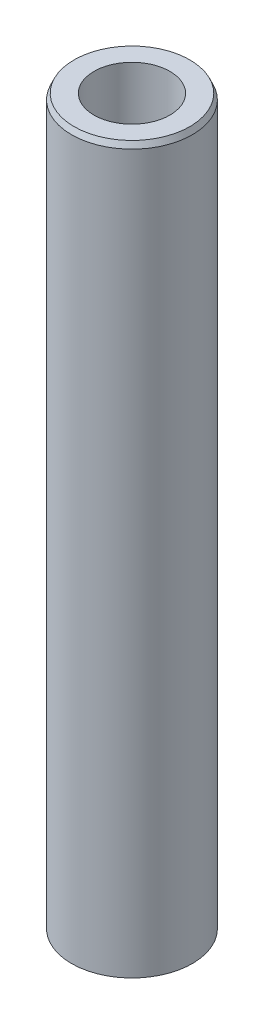
SolidWorks part; units mm, degrees
ref_plane "Front Plane" through (0, 0, 0) normal (0, 0, 1) x (1, 0, 0)
ref_plane "Top Plane" through (0, 0, 0) normal (0, 1, 0) x (1, 0, 0)
ref_plane "Right Plane" through (0, 0, 0) normal (1, 0, 0) x (0, 0, -1)
sketch "Sketch1" plane through (0, 0, 0) normal (0, 1, 0) x (1, 0, 0)
  circle A0 centre (0, 0) radius 27.5
  dimension "SHAFT_OD" = 55
extrude "Boss-Extrude1" add sketch "Sketch1" along normal blind 330.4615
sketch "Sketch2" plane through (0, 0, 0) normal (0, 1, 0) x (1, 0, 0)
  circle A0 centre (0, 0) radius 17.2671
  dimension "BORE_D" = 34.5343
extrude "Cut-Extrude1" cut sketch "Sketch2" along normal through all
chamfer "Chamfer1" distance 2.6095 angle 24.121 2 edges at (0, 330.4615, 27.5) (0, 0, 27.5) first distance on face at (0, 330.4615, 27.5) first distance on face at (0, 0, 17.2671)
